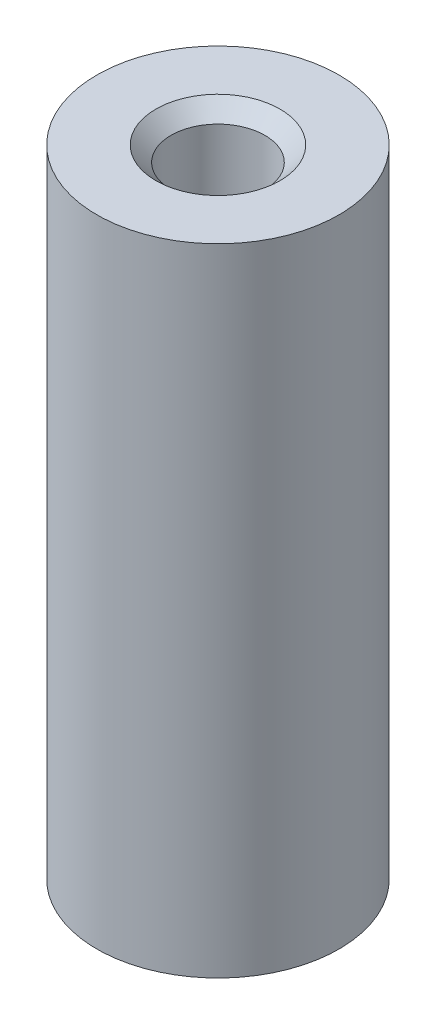
SolidWorks part; units mm, degrees
ref_plane "Ebene vorne" through (0, 0, 0) normal (0, 0, 1) x (1, 0, 0)
ref_plane "Ebene oben" through (0, 0, 0) normal (0, 1, 0) x (1, 0, 0)
ref_plane "Ebene rechts" through (0, 0, 0) normal (1, 0, 0) x (0, 0, -1)
sketch "Skizze1" plane through (0, 0, 0) normal (0, 1, 0) x (1, 0, 0)
  circle A0 centre (0, 0) radius 4
  dimension "D1" = 8
extrude "Aufsatz-Linear austragen1" add sketch "Skizze1" along normal blind 21
hole_wizard "Ø3.1 (3.1) Durchmesser Bohrung1" positions "Skizze2" profile "Skizze3" hole size "Ø3.1" standard "ISO" end condition through all
sketch "Skizze2" plane through (0, 21, 0) normal (0, 1, 0) x (1, 0, 0)
  point P4 (0, 0)
sketch "Skizze3" plane through (0, 21, 0) normal (1, 0, 0) x (0, 0, 1)
  line L0 (0, 0) -> (0, 21)
  line L1 (0, 21) -> (1.55, 21)
  line L2 (1.55, 21) -> (1.55, 0)
  line L5 (1.55, 0) -> (0, 0)
  line L11 (0, -6.35) -> (0, 107.95) construction
  dimension "Bohrerdurchmesser" = 3.1
  dimension "Bohrungstiefe" = 21
chamfer "Fase1" distance 0.5 angle 45 2 edges at (0, 0, 1.55) (0, 21, 1.55)
